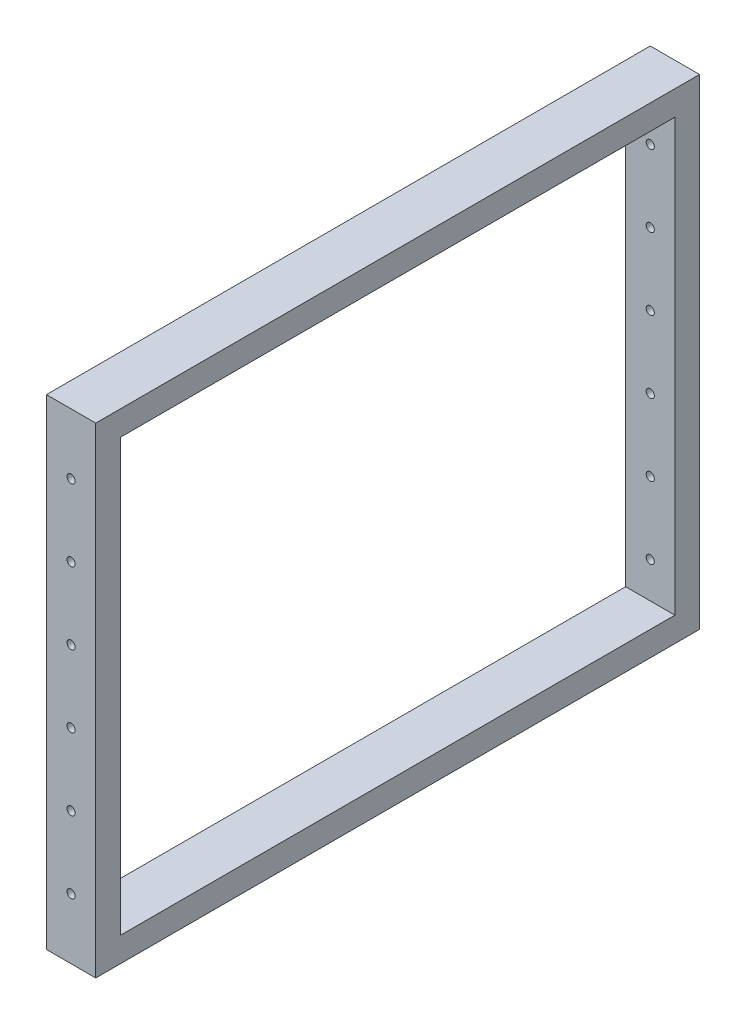
SolidWorks part; units mm, degrees
ref_plane "Front Plane" through (0, 0, 0) normal (0, 0, 1) x (1, 0, 0)
ref_plane "Top Plane" through (0, 0, 0) normal (0, 1, 0) x (1, 0, 0)
ref_plane "Right Plane" through (0, 0, 0) normal (1, 0, 0) x (0, 0, -1)
other "Configuration Table"
sketch "Sketch1" plane through (0, 0, 0) normal (1, 0, 0) x (0, 0, -1)
  line L1 (0, 0) -> (-490, 0)
  line L2 (0, 0) -> (0, 390)
  line L3 (0, 390) -> (-490, 390)
  line L4 (-490, 0) -> (-490, 390)
  line L5 (0, 0) -> (-490, 390) construction
  line L6 (0, 390) -> (-490, 0) construction
  point P0 (-245, 195)
extrude "frame" add sketch "Sketch1" along normal blind 40 from offset 0 separate body
sketch "Sketch2" plane through (0, 0, 0) normal (1, 0, 0) x (0, 0, -1)
  line L1 (-20, 20) -> (-470, 20)
  line L2 (-20, 20) -> (-20, 370)
  line L3 (-20, 370) -> (-470, 370)
  line L4 (-470, 20) -> (-470, 370)
  line L5 (-20, 20) -> (-470, 370) construction
  line L6 (-20, 370) -> (-470, 20) construction
  point P0 (-245, 195)
extrude "opening" add sketch "Sketch2" along normal blind 42 from offset 1 separate body offset against normal yes
combine bodies "Combine1" operation type subtract main body 102 bodies to subtract 103
sketch "Sketch3" plane through (0, 0, 0) normal (0, 0, 1) x (1, 0, 0)
  circle A0 centre (20, 49.1667) radius 3.3
extrude "pivot_0" add sketch "Sketch3" along normal blind 492 from offset 1 separate body offset against normal yes
combine bodies "Combine2" operation type subtract main body 104 bodies to subtract 105
sketch "Sketch4" plane through (0, 0, 0) normal (0, 0, 1) x (1, 0, 0)
  circle A0 centre (20, 107.5) radius 3.3
extrude "pivot_1" add sketch "Sketch4" along normal blind 492 from offset 1 separate body offset against normal yes
combine bodies "Combine3" operation type subtract main body 106 bodies to subtract 107
sketch "Sketch5" plane through (0, 0, 0) normal (0, 0, 1) x (1, 0, 0)
  circle A0 centre (20, 165.8333) radius 3.3
extrude "pivot_2" add sketch "Sketch5" along normal blind 492 from offset 1 separate body offset against normal yes
combine bodies "Combine4" operation type subtract main body 108 bodies to subtract 109
sketch "Sketch6" plane through (0, 0, 0) normal (0, 0, 1) x (1, 0, 0)
  circle A0 centre (20, 224.1667) radius 3.3
extrude "pivot_3" add sketch "Sketch6" along normal blind 492 from offset 1 separate body offset against normal yes
combine bodies "Combine5" operation type subtract main body 110 bodies to subtract 111
sketch "Sketch7" plane through (0, 0, 0) normal (0, 0, 1) x (1, 0, 0)
  circle A0 centre (20, 282.5) radius 3.3
extrude "pivot_4" add sketch "Sketch7" along normal blind 492 from offset 1 separate body offset against normal yes
combine bodies "Combine6" operation type subtract main body 112 bodies to subtract 113
sketch "Sketch8" plane through (0, 0, 0) normal (0, 0, 1) x (1, 0, 0)
  circle A0 centre (20, 340.8333) radius 3.3
extrude "pivot_5" add sketch "Sketch8" along normal blind 492 from offset 1 separate body offset against normal yes
combine bodies "Combine7" operation type subtract main body 114 bodies to subtract 115
